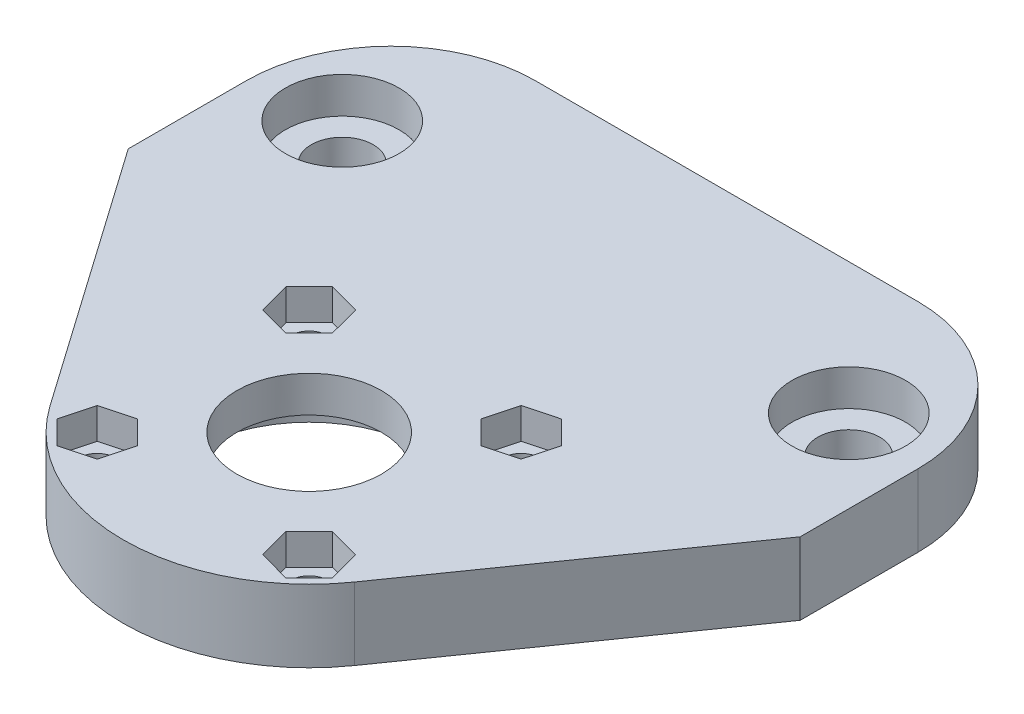
SolidWorks part; units mm, degrees
ref_plane "Front Plane" through (0, 0, 0) normal (0, 0, 1) x (1, 0, 0)
ref_plane "Top Plane" through (0, 0, 0) normal (0, 1, 0) x (1, 0, 0)
ref_plane "Right Plane" through (0, 0, 0) normal (1, 0, 0) x (0, 0, -1)
sketch "Sketch1" plane through (0, 0, 0) normal (0, 1, 0) x (1, 0, 0)
  line L0 (0, 0) -> (0, 15) construction
  line L1 (-32.5, 15) -> (32.5, 15) construction
  line L2 (-32.5, 15) -> (-32.5, 40.4)
  line L3 (-32.5, 40.4) -> (32.5, 40.4)
  line L4 (32.5, 40.4) -> (32.5, 15)
  line L5 (-32.5, 15) -> (-14.7385, -10.3333)
  line L6 (32.5, 15) -> (14.7385, -10.3333)
  circle A0 centre (0, 0) radius 7
  circle A1 centre (0, 0) radius 18 construction
  arc A2 (-14.7385, -10.3333) -> (14.7385, -10.3333) centre (0, 0) ccw
  point P8 (0, 15)
  dimension "D1" = 14
  dimension "D2" = 36
  dimension "D3" = 15
  dimension "D4" = 25.4
  dimension "D5" = 65
extrude "Boss-Extrude1" add sketch "Sketch1" along normal blind 7
sketch "Sketch2" plane through (0, 0, 0) normal (0, -1, 0) x (1, 0, 0)
  circle A0 centre (0, 0) radius 11.1
  dimension "D1" = 22.2
extrude "Cut-Extrude1" cut sketch "Sketch2" against normal blind 3.5
sketch "Sketch3" plane through (0, 7, 0) normal (0, 1, 0) x (1, 0, 0)
  line L0 (32.5, 27.7) -> (-32.5, 27.7) construction
  line L1 (32.5, 15) -> (32.5, 40.4) construction
  line L2 (-32.5, 40.4) -> (-32.5, 15) construction
  line L3 (0, 0) -> (0, 27.7) construction
  line L4 (0, 27.7) -> (-1.3723, 26.3277) construction
  circle A0 centre (24.5, 27.7) radius 5.5
  circle A1 centre (24.5, 27.7) radius 3
  circle A2 centre (-24.5, 27.7) radius 3
  circle A3 centre (-24.5, 27.7) radius 5.5
  dimension "D1" = 8
  dimension "D2" = 11
  dimension "D3" = 6
extrude "Cut-Extrude2" cut sketch "Sketch3" against normal blind 3.5
extrude "Cut-Extrude3" cut sketch "Sketch3<2>" against normal through all contours A1 | A2 region at (24.5, 7, -27.7) region at (-24.5, 7, -27.7)
sketch "Sketch3<2>" plane through (0, 7, 0) normal (0, 1, 0) x (1, 0, 0) same geometry as "Sketch3"
sketch "Sketch4" plane through (0, 0, 0) normal (0, -1, 0) x (1, 0, 0)
  line L0 (0, 0) -> (10.253, 10.253) construction
  line L1 (0, 0) -> (0, 5.0875) construction
  circle A1 centre (10.253, 10.253) radius 1.75
  circle A2 centre (10.253, -10.253) radius 1.75
  circle A3 centre (-10.253, -10.253) radius 1.75
  circle A4 centre (-10.253, 10.253) radius 1.75
  point P15 (0, 0)
  dimension "D1" = 45
  dimension "D2" = 3.5
  dimension "D3" = 14.5
  dimension "D4" = 4
extrude "Cut-Extrude4" cut sketch "Sketch4" against normal through all
sketch "Sketch5" plane through (0, 7, 0) normal (0, 1, 0) x (1, 0, 0)
  line L0 (13.3215, 11.0703) -> (11.0795, 13.319)
  line L1 (-11.0703, 13.3215) -> (-13.319, 11.0795)
  line L2 (-13.319, 11.0795) -> (-12.5018, 8.011)
  line L3 (-12.5018, 8.011) -> (-9.4358, 7.1846)
  line L4 (-9.4358, 7.1846) -> (-7.187, 9.4266)
  line L5 (-7.187, 9.4266) -> (-8.0043, 12.4951)
  line L6 (-8.0043, 12.4951) -> (-11.0703, 13.3215)
  line L7 (11.0795, 13.319) -> (8.011, 12.5018)
  line L8 (8.011, 12.5018) -> (7.1846, 9.4358)
  line L9 (7.1846, 9.4358) -> (9.4266, 7.187)
  line L10 (9.4266, 7.187) -> (12.4951, 8.0043)
  line L11 (12.4951, 8.0043) -> (13.3215, 11.0703)
  line L12 (11.0703, -13.3215) -> (13.319, -11.0795)
  line L13 (13.319, -11.0795) -> (12.5018, -8.011)
  line L14 (12.5018, -8.011) -> (9.4358, -7.1846)
  line L15 (9.4358, -7.1846) -> (7.187, -9.4266)
  line L16 (7.187, -9.4266) -> (8.0043, -12.4951)
  line L17 (8.0043, -12.4951) -> (11.0703, -13.3215)
  line L18 (-13.3215, -11.0703) -> (-11.0795, -13.319)
  line L19 (-11.0795, -13.319) -> (-8.011, -12.5018)
  line L20 (-8.011, -12.5018) -> (-7.1846, -9.4358)
  line L21 (-7.1846, -9.4358) -> (-9.4266, -7.187)
  line L22 (-9.4266, -7.187) -> (-12.4951, -8.0043)
  line L23 (-12.4951, -8.0043) -> (-13.3215, -11.0703)
  circle A0 centre (-10.253, 10.253) radius 3.25 construction
  circle A1 centre (10.253, 10.253) radius 3.25 construction
  circle A2 centre (10.253, -10.253) radius 3.25 construction
  circle A3 centre (-10.253, -10.253) radius 3.25 construction
  circle A4 centre (-10.253, 10.253) radius 2.75 construction
  circle A5 centre (10.253, 10.253) radius 3.25 construction
  circle A6 centre (10.253, 10.253) radius 2.75 construction
  circle A7 centre (10.253, -10.253) radius 3.25 construction
  circle A8 centre (10.253, -10.253) radius 2.75 construction
  circle A9 centre (-10.253, -10.253) radius 3.25 construction
  circle A10 centre (-10.253, -10.253) radius 2.75 construction
  point P3 (-7.1075, 9.4358)
  point P12 (0, 0)
  point P18 (-9.5373, 12.9083)
  point P48 (0, 0)
  dimension "D1" = 6.5
  dimension "D3" = 5.5
  dimension "D2" = 4
  dimension "D4" = 4
extrude "Cut-Extrude5" cut sketch "Sketch5" against normal blind 3
fillet "Fillet1" radius 14 2 edges at (-32.5, 3.5, -40.4) (32.5, 3.5, -40.4)
